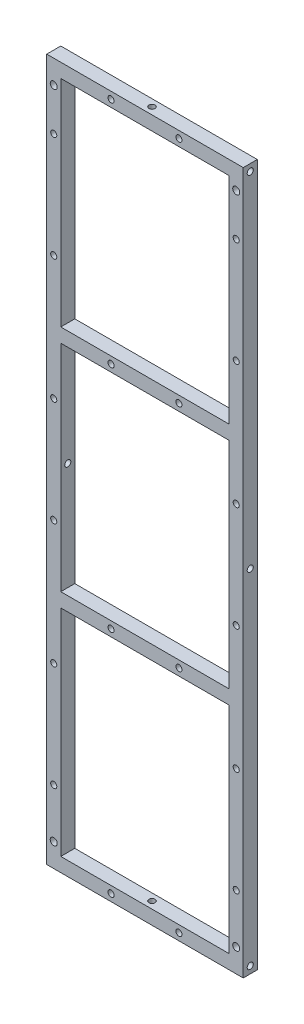
SolidWorks part; units mm, degrees
material "Alumina"
ref_plane "Front Plane" through (0, 0, 0) normal (0, 0, 1) x (1, 0, 0)
ref_plane "Top Plane" through (0, 0, 0) normal (0, 1, 0) x (1, 0, 0)
ref_plane "Right Plane" through (0, 0, 0) normal (1, 0, 0) x (0, 0, -1)
sketch "Sketch1" plane through (0, 0, 0) normal (0, 0, 1) x (1, 0, 0)
  line L0 (36, 144) -> (36, 52)
  line L9 (-42, -150) -> (42, -150)
  line L10 (-42, -150) -> (-42, 150)
  line L11 (-42, 150) -> (42, 150)
  line L12 (42, -150) -> (42, 150)
  line L13 (0, 0) -> (0, 46) construction
  line L15 (-36, -144) -> (36, -144)
  line L16 (-36, -144) -> (-36, -52)
  line L17 (-36, 144) -> (36, 144)
  line L21 (-36, 52) -> (36, 52)
  line L23 (-36, 46) -> (36, 46)
  line L25 (-36, -46) -> (36, -46)
  line L27 (-36, -52) -> (36, -52)
  line L33 (36, 46) -> (36, -46)
  line L34 (-36, 52) -> (-36, 144)
  line L35 (-36, -46) -> (-36, 46)
  line L36 (36, -52) -> (36, -144)
  point P0 (0, 0)
  point P24 (0, 0)
  dimension "D1" = 84
  dimension "D2" = 300
  dimension "D3" = 72
  dimension "D4" = 288
  dimension "D5" = 6
  dimension "D6" = 92
  dimension "D7" = 6
  dimension "D8" = 92
  dimension "D9" = 6
  dimension "D10" = 6
  dimension "D11" = 92
  dimension "D12" = 46
  dimension "D13" = 6
extrude "Boss-Extrude1" add sketch "Sketch1" along normal blind 6
sketch "Sketch2" plane through (42, 0, 0) normal (1, 0, 0) x (0, 0, -1)
  line L0 (-6, 150) -> (0, 150) construction
  line L1 (-6, -150) -> (-6, 150) construction
  line L3 (-3, 147) -> (-3, 0) construction
  circle A0 centre (-3, 147) radius 1.3
  circle A4 centre (-3, 0) radius 1.3
  circle A5 centre (-3, -147) radius 1.3
  circle A6 centre (-3, -294) radius 1.3
  dimension "D1" = 3
  dimension "D3" = 2.6
  dimension "D4" = 3
  dimension "D2" = 4
  dimension "D5" = 147
extrude "Cut-Extrude1" cut sketch "Sketch2" against normal blind 10
mirror "Mirror1" about plane through (0, 0, 0) normal (1, 0, 0) of "Cut-Extrude1"
sketch "Sketch4" plane through (0, 0, 6) normal (0, 0, 1) x (1, 0, 0)
  line L0 (-42, -150) -> (-42, 150) construction
  line L1 (42, -150) -> (42, 150) construction
  line L2 (-42, 150) -> (42, 150) construction
  line L3 (42, 150) -> (-42, 150) construction
  line L4 (-14.5, 147) -> (-14.5, 49) construction
  line L6 (-39, 122) -> (39, 122) construction
  line L7 (-39, 122) -> (-39, 77) construction
  line L8 (-39, 122) -> (-39, 24) construction
  circle A0 centre (-14.5, 147) radius 1.3
  circle A1 centre (14.5, 147) radius 1.3
  circle A8 centre (-39, 122) radius 1.3
  circle A20 centre (-14.5, 49) radius 1.3
  circle A21 centre (14.5, 49) radius 1.3
  circle A22 centre (-14.5, -49) radius 1.3
  circle A23 centre (14.5, -49) radius 1.3
  circle A24 centre (-14.5, -147) radius 1.3
  circle A25 centre (14.5, -147) radius 1.3
  circle A29 centre (39, 122) radius 1.3
  circle A30 centre (39, 77) radius 1.3
  circle A31 centre (-39, 77) radius 1.3
  circle A32 centre (-39, 24) radius 1.3
  circle A33 centre (39, 24) radius 1.3
  circle A34 centre (39, -21) radius 1.3
  circle A35 centre (-39, -21) radius 1.3
  circle A36 centre (-39, -74) radius 1.3
  circle A37 centre (39, -74) radius 1.3
  circle A38 centre (39, -119) radius 1.3
  circle A39 centre (-39, -119) radius 1.3
  dimension "D1" = 27.5
  dimension "D4" = 78
  dimension "D7" = 45
  dimension "D10" = 2.6
  dimension "D11" = 2.6
  dimension "D3" = 3
  dimension "D6" = 3
  dimension "D14" = 2.6
  dimension "D15" = 2
  dimension "D16" = 98
  dimension "D2" = 27.5
  dimension "D5" = 28
  dimension "D9" = 3
  dimension "D13" = 98
  dimension "D12" = 4
  dimension "D8" = 2
extrude "Cut-Extrude3" cut sketch "Sketch4" against normal blind 10
sketch "Sketch5" plane through (0, 150, 0) normal (0, 1, 0) x (1, 0, 0)
  line L0 (42, -6) -> (-42, -6) construction
  circle A0 centre (0, -3) radius 1.3
  point P5 (0, -6)
  dimension "D1" = 3
  dimension "D2" = 2.6
extrude "Cut-Extrude4" cut sketch "Sketch5" against normal blind 10
mirror "Mirror2" about plane through (0, 0, 0) normal (0, 1, 0) of "Cut-Extrude4"
sketch "Sketch6" plane through (0, 0, 6) normal (0, 0, 1) x (1, 0, 0)
  line L0 (-42, 150) -> (-42, -150) construction
  line L1 (42, 150) -> (-42, 150) construction
  circle A0 centre (-39, 140) radius 1.5
  dimension "D1" = 3
  dimension "D2" = 3
  dimension "D3" = 10
extrude "Cut-Extrude5" cut sketch "Sketch6" against normal blind 10
pattern_linear "LPattern1" count 2 spacing 78 along (1, 0, 0) count 2 spacing 280 along (0, -1, 0) of "Cut-Extrude5"
